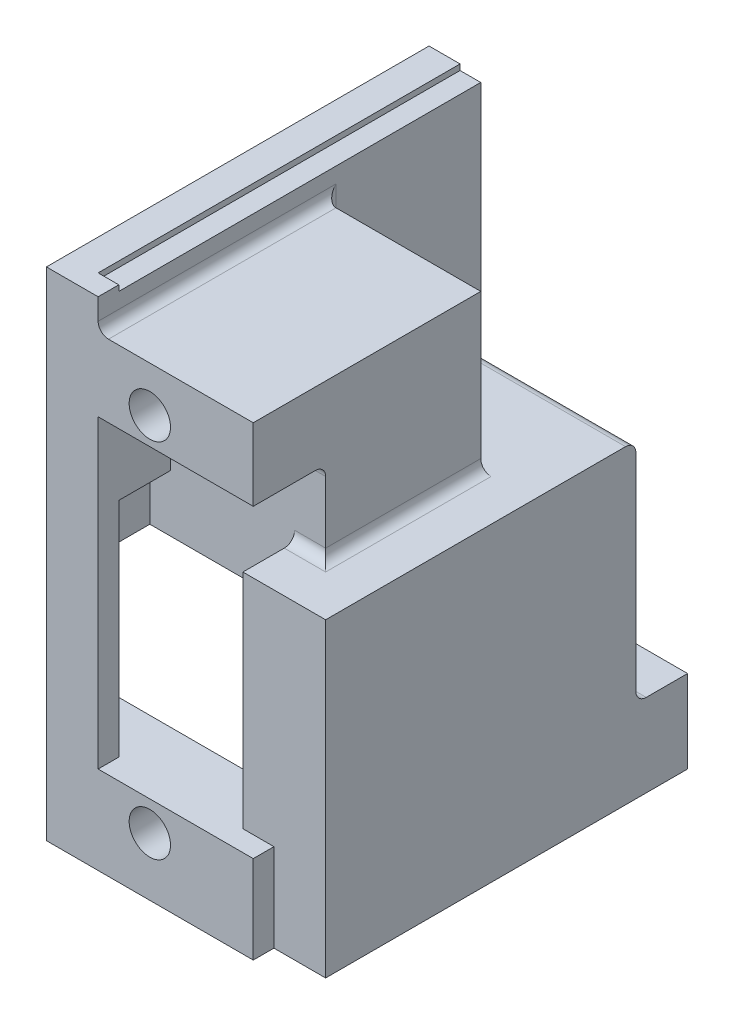
SolidWorks part; units mm, degrees
note: The reader was unsure of these and kept them because the rebuilt part matched: shared geometry of "草圖14<6>".
other "標示1"
sketch "草圖16" plane through (-15, 15, -55) normal (-0.0488, 0.9988, -0.0094) x (0.0609, 0.0124, 0.9981)
material "ABS"
ref_plane "前基準面" through (0, 0, 0) normal (0, 0, 1) x (1, 0, 0)
ref_plane "上基準面" through (0, 0, 0) normal (0, 1, 0) x (1, 0, 0)
ref_plane "右基準面" through (0, 0, 0) normal (1, 0, 0) x (0, 0, -1)
sketch "草圖2" plane through (0, 0, 0) normal (0, 0, 1) x (1, 0, 0)
  line L1 (-15, 15) -> (15, 15)
  line L2 (-15, 15) -> (-15, -15)
  line L3 (-15, -15) -> (15, -15)
  line L4 (15, 15) -> (15, -15)
  line L5 (-15, 15) -> (15, -15) construction
  line L6 (-15, -15) -> (15, 15) construction
  point P0 (0, 0)
  dimension "D2" = 30
  dimension "D1" = 30
extrude "填料-伸長2" add sketch "草圖2" along normal mid plane 30
sketch "草圖3" plane through (0, 15, 0) normal (0, 1, 0) x (1, 0, 0)
  line L0 (6, 15) -> (6, -10)
  line L1 (15, 15) -> (-15, 15) construction
  line L2 (6, -10) -> (-15, -10)
  line L3 (-15, -15) -> (-15, 15) construction
  line L4 (-15, -10) -> (-15, 15)
  line L5 (-15, 15) -> (6, 15)
  dimension "D1" = 25
  dimension "D2" = 21
extrude "除料-伸長1" cut sketch "草圖3" against normal blind 24.5
sketch "草圖4" plane through (0, 0, 15) normal (0, 0, 1) x (1, 0, 0)
  circle A0 centre (0, 0) radius 5
  dimension "D1" = 10
extrude "除料-伸長2" cut sketch "草圖4" against normal through all
sketch "草圖5" plane through (0, 0, 0) normal (0, 0, 1) x (1, 0, 0)
  line L0 (0, 14) -> (6, 14)
  line L1 (6, 14) -> (6, 6)
  line L4 (6, -9.5) -> (6, 15) construction
  line L5 (6, 6) -> (6, 3)
  line L6 (6, 3) -> (0, 6)
  arc A0 (0, 14) -> (0, 6) centre (0, 10) ccw
  dimension "D2" = 8
  dimension "D1" = 10
  dimension "D3" = 3
extrude "填料-伸長3" add sketch "草圖5" along normal mid plane 5 separate body
sketch "草圖6" plane through (0, 0, -15) normal (0, 0, -1) x (-1, 0, 0)
  line L0 (-15, 15) -> (-6, 15) construction
  line L1 (-7, 15) -> (7, 15)
  line L2 (-7, 15) -> (-7, -15)
  line L3 (-7, -15) -> (7, -15)
  line L4 (7, 15) -> (7, -15)
  line L5 (15, -15) -> (-6, -15) construction
  line L6 (0, 15) -> (0, -15) construction
  dimension "D1" = 14
extrude "除料-伸長3" cut sketch "草圖6" against normal blind 5
sketch "草圖8" plane through (0, 0, 0) normal (0, 0, 1) x (1, 0, 0)
  circle A0 centre (0, 10) radius 2
  dimension "D1" = 4
extrude "除料-伸長4" cut sketch "草圖8" against normal mid plane 5
sketch "草圖9" plane through (-15, 0, 0) normal (-1, 0, 0) x (0, 0, 1)
  line L1 (-45, 15) -> (-10, 15)
  line L2 (-45, 15) -> (-45, -125)
  line L3 (-45, -125) -> (-10, -125)
  line L4 (155, 15) -> (155, -125)
  line L5 (10, 15) -> (-10, 15) construction
  line L6 (-855, -55) -> (49145, -55) construction
  line L7 (55, -985) -> (55, 49015) construction
  line L9 (-10, 15) -> (-10, -9.5)
  line L10 (-10, -9.5) -> (10, -9.5)
  line L11 (10, -9.5) -> (10, 15)
  line L12 (10, 15) -> (100, 15)
  line L13 (10, -100.5) -> (10, -125)
  line L14 (-10, -100.5) -> (10, -100.5)
  line L15 (-10, -125) -> (-10, -100.5)
  line L16 (100, -100.5) -> (100, -125)
  line L17 (120, -125) -> (120, -100.5)
  line L18 (120, -100.5) -> (100, -100.5)
  line L19 (100, -9.5) -> (100, 15)
  line L20 (120, -9.5) -> (100, -9.5)
  line L21 (120, 15) -> (120, -9.5)
  line L22 (120, 15) -> (155, 15)
  line L23 (120, -125) -> (155, -125)
  line L24 (10, -125) -> (100, -125)
  line L25 (-15, -9.5) -> (10, -9.5) construction
  line L27 (10, -9.5) -> (10, 15) construction
  point P9 (155, -55)
  dimension "D1" = 200
  dimension "D2" = 140
  dimension "D3" = 35
  dimension "D4" = 20
extrude "填料-伸長4" add sketch "草圖9" against normal blind 10
ref_plane "平面1" through (0, 0, 55) normal (0, 0, 1) x (1, 0, 0)
ref_plane "平面2" through (0, -55, 0) normal (0, 1, 0) x (1, 0, 0)
mirror "鏡射18" about plane through (0, -55, 0) normal (0, 1, 0) of "除料-伸長2", "除料-伸長1", "填料-伸長2"
mirror "鏡射14" about plane through (0, -55, 0) normal (0, 1, 0) of "除料-伸長4", "填料-伸長3"
mirror "鏡射19" about plane through (0, 0, 55) normal (0, 0, 1) of "除料-伸長3" second plane through (0, -55, 0) second plane normal (0, 1, 0)
sketch "草圖10" plane through (-15, 0, 0) normal (-1, 0, 0) x (0, 0, 1)
  line L0 (100, 15) -> (10, 15) construction
  line L9 (-1145, -55) -> (48855, -55) construction
  line L10 (10, -125) -> (100, -125) construction
  line L11 (55, -1125) -> (55, 48875) construction
  line L21 (100, 15) -> (10, 15)
  line L22 (100, 15) -> (100, 7)
  line L23 (100, 7) -> (10, 7)
  line L24 (10, 15) -> (10, 7)
  line L25 (100, -117) -> (10, -117)
  line L26 (10, -125) -> (10, -117)
  line L27 (100, -125) -> (10, -125)
  line L28 (100, -125) -> (100, -117)
  point P3 (55, -125)
  dimension "D2" = 90
  dimension "D3" = 8
extrude "填料-伸長5" add sketch "草圖10" against normal blind 30
sketch "草圖11" plane through (-5, 0, 0) normal (1, 0, 0) x (0, 0, -1)
  line L5 (10, 6.5) -> (17, 6.5)
  line L6 (17, 15) -> (17, 6.5)
  line L7 (10, 15) -> (17, 15)
  line L8 (10, 15) -> (10, 6.5)
  line L9 (19.25, -55) -> (-19.25, -55) construction
  line L10 (10, -125) -> (10, -116.5)
  line L11 (10, -125) -> (17, -125)
  line L12 (17, -125) -> (17, -116.5)
  line L13 (10, -116.5) -> (17, -116.5)
  line L27 (12.9732, -80) -> (17, -80)
  line L28 (17, -87) -> (17, -80)
  line L29 (10, -87) -> (17, -87)
  line L34 (-55, 19.25) -> (-55, -19.25) construction
  line L35 (-120, -125) -> (-127, -125)
  line L36 (-127, -125) -> (-127, -116.5)
  line L37 (-120, -125) -> (-120, -116.5)
  line L38 (-120, -116.5) -> (-127, -116.5)
  line L39 (-120, -87) -> (-127, -87)
  line L40 (-127, -87) -> (-127, -80)
  line L42 (10, -23) -> (17, -23)
  line L43 (17, -23) -> (17, -30)
  line L44 (12.9732, -30) -> (17, -30)
  line L50 (-122.9732, -80) -> (-127, -80)
  line L51 (-122.9732, -30) -> (-127, -30)
  line L52 (-127, -23) -> (-127, -30)
  line L54 (-120, -23) -> (-127, -23)
  line L55 (-120, 15) -> (-120, 6.5)
  line L56 (-120, 15) -> (-127, 15)
  line L57 (-120, 6.5) -> (-127, 6.5)
  line L58 (-127, 15) -> (-127, 6.5)
  line L59 (-5, -15) -> (10, -15)
  line L60 (-5, -15) -> (-5, -30)
  line L61 (-5, -30) -> (12.9732, -30)
  line L62 (10, -15) -> (10, -23)
  line L63 (-105, -30) -> (-122.9732, -30)
  line L64 (-120, -15) -> (-120, -23)
  line L65 (-105, -15) -> (-120, -15)
  line L66 (-105, -15) -> (-105, -30)
  line L67 (-5, -80) -> (12.9732, -80)
  line L68 (10, -95) -> (10, -87)
  line L69 (-5, -95) -> (10, -95)
  line L70 (-5, -95) -> (-5, -80)
  line L71 (-105, -80) -> (-122.9732, -80)
  line L72 (-105, -95) -> (-105, -80)
  line L73 (-105, -95) -> (-120, -95)
  line L74 (-120, -95) -> (-120, -87)
  dimension "D2" = 8.5
  dimension "D3" = 7
  dimension "D4" = 29.5
  dimension "D5" = 10
  dimension "D1" = 15
  dimension "D6" = 15
extrude "填料-伸長6" add sketch "草圖11" along normal blind 15 and the other way blind 10
sketch "草圖12" plane through (-5, 0, 0) normal (1, 0, 0) x (0, 0, -1)
  line L0 (19.25, -55) -> (-19.25, -55) construction
  line L1 (-125, -77.5) -> (15, -77.5)
  line L2 (-125, -77.5) -> (-125, -32.5)
  line L3 (-125, -32.5) -> (15, -32.5)
  line L4 (15, -77.5) -> (15, -32.5)
  line L5 (-125, -77.5) -> (15, -32.5) construction
  line L6 (-125, -32.5) -> (15, -77.5) construction
  line L7 (-55, 19.25) -> (-55, -19.25) construction
  point P0 (-55, -55)
  dimension "D1" = 45
  dimension "D2" = 140
extrude "除料-伸長5" cut sketch "草圖12" against normal blind 2
sketch "草圖15" plane through (-5, 0, 0) normal (1, 0, 0) x (0, 0, -1)
  line L0 (-55, 16.5) -> (-55, -16.5) construction
  line L1 (16.5, -55) -> (-16.5, -55) construction
  line L3 (-146.5057, -35) -> (-131.5057, -35)
  line L4 (-155, -125) -> (-155, 15) construction
  line L5 (45, 15) -> (45, -125) construction
  line L6 (-146.5057, -35) -> (-146.5057, -75)
  line L7 (-146.5057, -75) -> (-131.5057, -75)
  line L8 (-131.5057, -35) -> (-131.5057, -75)
  line L20 (36.5057, -75) -> (21.5057, -75)
  line L21 (21.5057, -35) -> (21.5057, -75)
  line L22 (36.5057, -35) -> (21.5057, -35)
  line L23 (36.5057, -35) -> (36.5057, -75)
  line L25 (-90, -10) -> (-65, -10)
  line L26 (-90, -10) -> (-90, -50)
  line L27 (-90, -50) -> (-65, -50)
  line L28 (-65, -10) -> (-65, -50)
  line L29 (-90, -60) -> (-65, -60)
  line L30 (-65, -100) -> (-65, -60)
  line L31 (-90, -100) -> (-65, -100)
  line L32 (-90, -100) -> (-90, -60)
  line L33 (-20, -100) -> (-20, -60)
  line L34 (-20, -100) -> (-45, -100)
  line L35 (-45, -100) -> (-45, -60)
  line L36 (-20, -60) -> (-45, -60)
  line L37 (-20, -50) -> (-45, -50)
  line L38 (-45, -10) -> (-45, -50)
  line L39 (-20, -10) -> (-45, -10)
  line L40 (-20, -10) -> (-20, -50)
  line L41 (-146.5057, -112.7357) -> (-131.5057, -112.7357)
  line L42 (-146.5057, -9.1261) -> (-131.5057, -9.1261)
  line L43 (-146.5057, -9.1261) -> (-146.5057, 2.7357)
  line L44 (-146.5057, 2.7357) -> (-131.5057, 2.7357)
  line L45 (-131.5057, -9.1261) -> (-131.5057, 2.7357)
  line L46 (-131.5057, -100.8739) -> (-131.5057, -112.7357)
  line L47 (-146.5057, -100.8739) -> (-131.5057, -100.8739)
  line L48 (-146.5057, -100.8739) -> (-146.5057, -112.7357)
  line L49 (36.5057, -100.8739) -> (36.5057, -112.7357)
  line L50 (36.5057, -100.8739) -> (21.5057, -100.8739)
  line L51 (21.5057, -100.8739) -> (21.5057, -112.7357)
  line L52 (36.5057, -112.7357) -> (21.5057, -112.7357)
  line L53 (36.5057, 2.7357) -> (21.5057, 2.7357)
  line L54 (21.5057, -9.1261) -> (21.5057, 2.7357)
  line L55 (36.5057, -9.1261) -> (21.5057, -9.1261)
  line L56 (36.5057, -9.1261) -> (36.5057, 2.7357)
  circle A0 centre (30, -90) radius 2.5
  circle A1 centre (-55, -90) radius 2.5
  circle A2 centre (-140, -90) radius 2.5
  circle A3 centre (-140, -20) radius 2.5
  circle A4 centre (30, -20) radius 2.5
  circle A5 centre (-55, -20) radius 2.5
  dimension "D2" = 15
  dimension "D4" = 5
  dimension "D5" = 5
  dimension "D6" = 5
  dimension "D1" = 35
  dimension "D3" = 15
  dimension "D7" = 20
  dimension "D8" = 20
  dimension "D9" = 15
  dimension "D10" = 10
  dimension "D11" = 5
  dimension "D12" = 25
  dimension "D13" = 40
extrude "除料-伸長7" cut sketch "草圖15" against normal through all
sketch "草圖14" plane through (15, 0, 0) normal (1, 0, 0) x (0, 0, -1)
  line L0 (-55, 16.5) -> (-55, -16.5) construction
  line L1 (-125, 15) -> (15, 15) construction
  line L2 (45, 15) -> (45, -125) construction
  line L4 (16.5, -55) -> (-16.5, -55) construction
  line L5 (17, 15) -> (45, 15) construction
  circle A0 centre (-55, 11) radius 2
  circle A1 centre (39, 9) radius 2
  circle A2 centre (-149, 9) radius 2
  circle A3 centre (39, -119) radius 2
  circle A4 centre (-55, -121) radius 2
  circle A5 centre (-149, -119) radius 2
  dimension "D1" = 4
  dimension "D3" = 4
  dimension "D2" = 4
  dimension "D4" = 6
  dimension "D5" = 6
extrude "除料-伸長6" cut sketch "草圖14" against normal blind 5 contours A0 | A4
fillet "圓角1" radius 5 12 edges at (-10, -125, 155) (-10, 15, 155) (-10, 15, -45) (-10, -125, -45) (-10, -75, -36.5057) (-10, -35, -21.5057) (-10, -75, -21.5057) (-10, -35, -36.5057) (-10, -75, 146.5057) (-10, -75, 131.5057) (-10, -35, 131.5057) (-10, -35, 146.5057)
sketch "草圖17" plane through (0, 0, -17) normal (0, 0, -1) x (-1, 0, 0)
  line L1 (16.5, -55) -> (-16.5, -55) construction
  circle A0 centre (0, 9.38) radius 2
  circle A1 centre (0, -25.62) radius 2
  circle A2 centre (0, -84.38) radius 2
  circle A3 centre (0, -119.38) radius 2
  dimension "D1" = 4
extrude "除料-伸長8" cut sketch "草圖17" against normal blind 5
mirror "鏡射20" about plane through (0, 0, 55) normal (0, 0, 1) of "除料-伸長8"
extrude "除料-伸長9" cut sketch "草圖14<6>" against normal blind 25 contours A5 | A3 | A1 | A2
sketch "草圖14<6>" plane through (15, 0, 0) normal (1, 0, 0) x (0, 0, -1) same geometry as "草圖14"
sketch "草圖18" plane through (-5, 0, 0) normal (1, 0, 0) x (0, 0, -1)
  circle A0 centre (30, -90) radius 4.3
  circle A1 centre (-55, -90) radius 4.3
  circle A2 centre (-140, -90) radius 4.3
  circle A3 centre (-140, -20) radius 4.3
  circle A4 centre (-55, -20) radius 4.3
  circle A5 centre (30, -20) radius 4.3
  dimension "D1" = 8.6
extrude "除料-伸長10" cut sketch "草圖18" against normal blind 6
fillet "圓角2" radius 1 28 edges at (5, -15, 95) (5, -95, 15) (5, -95, 95) (-5, 7, 55) (5, 7, 15) (5, 7, 95) (-5, -117, 55) (5, -117, 15) (5, -117, 95) (-5, -80, 116) (2.5, -87, 120) (8.5, -95, 120) (-5, -87.5, 105) (10, -95, 112.5) (-5, -22.5, 105) (-5, -30, 116) (2.5, -23, 120) (8.5, -15, 120) (10, -15, 112.5) (-5, -30, -6) (8.5, -15, -10) (2.5, -23, -10) (10, -15, -2.5) (5, -15, 15) (-5, -80, -6) (2.5, -87, -10) (8.5, -95, -10) (10, -95, -2.5)
sketch "草圖19" plane through (0, -55, 0) normal (0, 1, 0) x (1, 0, 0)
  line L0 (-5, -20) -> (-5, -38.6232)
  line L1 (-5, -38.6232) -> (10, -20)
  line L2 (10, -20) -> (-5, -20)
  line L3 (10, -26.3768) -> (-5, -45)
  line L4 (-5, -45) -> (10, -45)
  line L5 (10, -45) -> (10, -26.3768)
  line L6 (-16.5, -55) -> (16.5, -55) construction
  line L7 (10, -90) -> (-5, -90)
  line L8 (-5, -90) -> (-5, -71.3768)
  line L9 (-5, -71.3768) -> (10, -90)
  line L10 (-5, -65) -> (10, -65)
  line L11 (10, -83.6232) -> (-5, -65)
  line L12 (10, -65) -> (10, -83.6232)
  line L13 (-15, -100) -> (-15, -10) construction
  line L14 (15, -125) -> (15, 15) construction
  line L15 (15, -15) -> (-5, -15) construction
  line L16 (-15, 45) -> (-5, 45) construction
  line L17 (-10, 45) -> (-15, 45)
  line L18 (-10, 45) -> (-10, -155)
  line L19 (-10, -155) -> (-15, -155)
  line L20 (-15, 45) -> (-15, -155)
  line L21 (-15, -150) -> (-15, -155) construction
  dimension "D1" = 10
  dimension "D2" = 5
  dimension "D3" = 4
  dimension "D4" = 20
  dimension "D5" = 5
  dimension "D6" = 5
extrude "除料-伸長11" cut sketch "草圖19" against normal through all both and the other way through all
sketch "草圖20" plane through (15, 0, 0) normal (1, 0, 0) x (0, 0, -1)
  line L0 (-127, -125) -> (-127, -76.9486)
  line L1 (-127, -76.9486) -> (-90, -76.9486)
  line L2 (-90, -77.5) -> (-90, -60) construction
  line L3 (-90, -76.9486) -> (-90, -125)
  line L4 (-90, -125) -> (55.0247, -125)
  line L5 (55.0247, -125) -> (55.0247, 33.1142)
  line L6 (55.0247, 33.1142) -> (-156.1879, 33.1142)
  line L7 (-156.1879, 33.1142) -> (-156.1879, -125)
  line L8 (-156.1879, -125) -> (-127, -125)
extrude "除料-伸長12" cut sketch "草圖20" against normal through all
